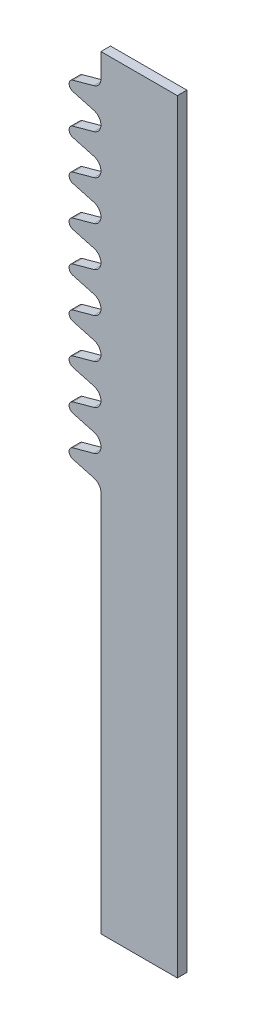
SolidWorks part; units mm, degrees
ref_plane "Front Plane" through (0, 0, 0) normal (0, 0, 1) x (1, 0, 0)
ref_plane "Top Plane" through (0, 0, 0) normal (0, 1, 0) x (1, 0, 0)
ref_plane "Right Plane" through (0, 0, 0) normal (1, 0, 0) x (0, 0, -1)
sketch "Sketch1" plane through (0, 0, 0) normal (0, 0, 1) x (1, 0, 0)
  line L1 (-1.7, -12) -> (1.7, -12)
  line L2 (-1.7, -12) -> (-1.7, 12)
  line L3 (-1.7, 12) -> (1.7, 12)
  line L4 (1.7, -12) -> (1.7, 12)
  line L5 (-1.7, -12) -> (1.7, 12) construction
  line L6 (-1.7, 12) -> (1.7, -12) construction
  point P0 (0, 0)
  dimension "D1" = 3.4
  dimension "D2" = 24
extrude "Boss-Extrude1" add sketch "Sketch1" against normal blind 0.3
sketch "Sketch2" plane through (0, 0, 0) normal (0, 0, 1) x (1, 0, 0)
  line L0 (-0.7, -12) -> (-0.7, 0)
  line L1 (-1.7, -12) -> (1.7, -12) construction
  line L2 (-1.7, 0.625) -> (-0.2197, 0.625) construction
  line L3 (-1.7, 12) -> (-1.7, -12) construction
  line L4 (-1.5823, 0.4707) -> (-0.9207, 0.2893)
  line L5 (-1.5823, 0.7793) -> (-0.9207, 0.9607)
  line L6 (-1, 0) -> (-1.9098, 0) construction
  line L7 (-1.5823, 1.7207) -> (-0.9207, 1.5393)
  line L8 (-1.7, 1.875) -> (-2.2, 1.875)
  line L9 (-1, 1.25) -> (-1.9098, 1.25) construction
  line L10 (-0.8181, 2.2388) -> (0.0637, 2.4805) [skipped]
  line L11 (-1.7, 0.625) -> (-2.2, 0.625)
  line L12 (-0.7, -12) -> (-2.2, -12)
  line L13 (-2.2, 12) -> (-2.2, -12)
  line L14 (-2.2, 1.875) -> (-2.2, -12)
  arc A0 (-1.5823, 0.4707) -> (-1.5823, 0.7793) centre (-1.54, 0.625) cw
  arc A1 (-0.7, 0) -> (-0.9207, 0.2893) centre (-1, 0) ccw
  arc A2 (-1.5823, 1.7207) -> (-1.7, 1.875) centre (-1.54, 1.875) cw
  arc A3 (-0.9207, 0.9607) -> (-0.9207, 1.5393) centre (-1, 1.25) ccw
  point P14 (-0.7, 0.2288)
  line M16 (-1.7, 12) -> (-1.7, -12)
  line M17 (-1.7, -12) -> (1.7, -12)
  dimension "D2" = 0.16
  dimension "D3" = 0.3
  dimension "D1" = 1
  dimension "D4" = 0.625
  dimension "D5" = 12
  dimension "D7" = 1.25
  dimension "D8" = 0.5
  dimension "D6" = 2
extrude "Cut-Extrude1" cut sketch "Sketch2" against normal through all contours L0 A1 L4 A0 M16 M17 region at (-1.2023, -5.8202, 0)
extrude "Cut-Extrude2" cut sketch "Sketch2<3>" against normal through all contours L5 A3 L7 A2 A0 M16 region at (-1.2801, 1.25, 0)
sketch "Sketch2<3>" plane through (0, 0, 0) normal (0, 0, 1) x (1, 0, 0) same geometry as "Sketch2"
pattern_linear "LPattern1" count 9 spacing 1.25 along (0, 1, 0) of "Cut-Extrude2"
sketch "Sketch3" plane through (0, 0, 0) normal (0, 0, 1) x (1, 0, 0)
  line L0 (1.7, 12) -> (-1.7, 12) construction
  line L2 (-0.7, 11.25) -> (-1.7, 11.25)
  line L3 (-0.7, 11.25) -> (-0.7, 12)
  line L4 (-0.7, 12) -> (-1.7, 12)
  line L5 (-1.7, 11.25) -> (-1.7, 12)
  line L6 (-1.7, 12) -> (-1.7, 11.875) construction
  arc A2 (-0.9207, 10.9607) -> (-0.9207, 11.5393) centre (-1, 11.25) ccw construction
extrude "Cut-Extrude3" cut sketch "Sketch3" against normal through all
